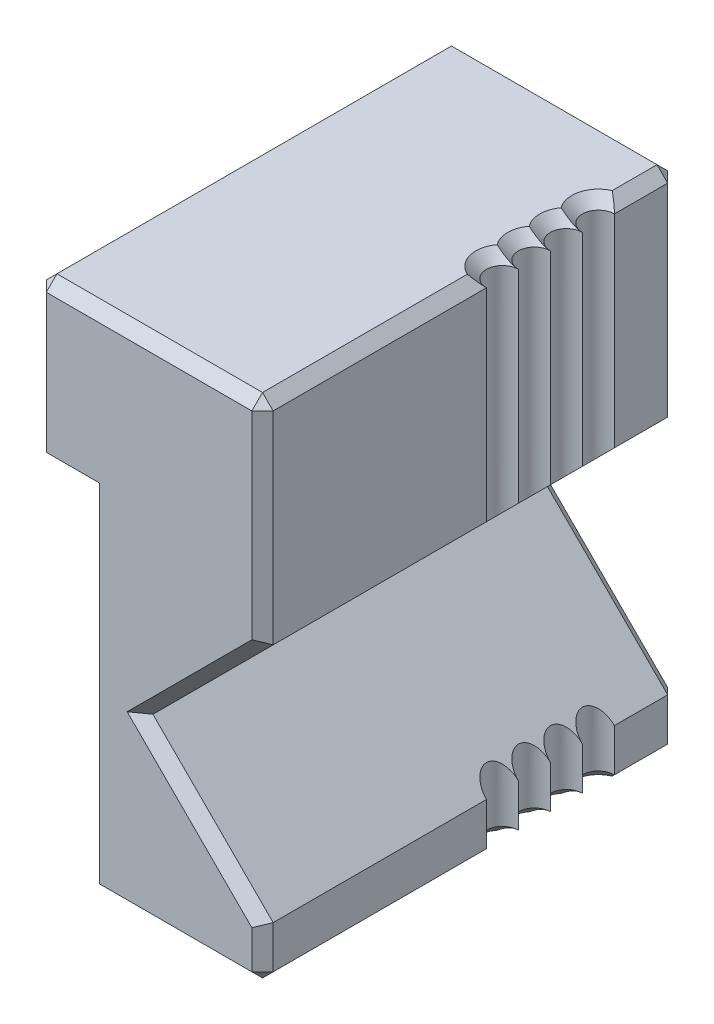
SolidWorks part; units mm, degrees
ref_plane "Front Plane" through (0, 0, 0) normal (0, 0, 1) x (1, 0, 0)
ref_plane "Top Plane" through (0, 0, 0) normal (0, 1, 0) x (1, 0, 0)
ref_plane "Right Plane" through (0, 0, 0) normal (1, 0, 0) x (0, 0, -1)
sketch "Sketch1" plane through (0, 0, 0) normal (0, 0, 1) x (1, 0, 0)
  line L0 (-11.2784, 0) -> (0, 11.2784)
  line L1 (0, 11.2784) -> (0, 31.2784)
  line L2 (0, 31.2784) -> (-21.2784, 31.2784)
  line L3 (-21.2784, 31.2784) -> (-21.2784, 16.2784)
  line L4 (-21.2784, 16.2784) -> (-16.2784, 16.2784)
  line L5 (-16.2784, 16.2784) -> (-16.2784, -16.2784)
  line L6 (-16.2784, -16.2784) -> (0, -16.2784)
  line L7 (0, -16.2784) -> (0, -11.2784)
  line L8 (0, -11.2784) -> (-11.2784, 0)
  circle A0 centre (0, 0) radius 7.975 construction
  dimension "D1" = 15.95
  dimension "D2" = 0
  dimension "D3" = 5
  dimension "D4" = 15
  dimension "D5" = 5
  dimension "D6" = 5
  dimension "D7" = 20
extrude "Boss-Extrude1" add sketch "Sketch1" along normal blind 39
sketch "Sketch2" plane through (0, 31.2784, 0) normal (0, 1, 0) x (1, 0, 0)
  circle A0 centre (0, -7.5) radius 1.5
  dimension "D1" = 3
  dimension "D2" = 6
extrude "Cut-Extrude1" cut sketch "Sketch2" against normal through all
pattern_linear "LPattern2" count 10 spacing 3 along (0, 0, 1) skipping (4, 0), (5, 0), (6, 0), (7, 0), (8, 0), (9, 0) of "Cut-Extrude1"
chamfer "Chamfer2" distance 1 angle 45 33 edges at (-1.5, 31.2784, 16.5) (-1.5, 31.2784, 13.5) (-1.5, 31.2784, 10.5) (-1.5, 31.2784, 7.5) (0, 31.2784, 3) (-1.5, -16.2784, 16.5) (-1.5, -16.2784, 13.5) (-1.5, -16.2784, 10.5) (-1.5, -16.2784, 7.5) (0, -16.2784, 3) (0, -13.7784, 39) (-8.1392, -16.2784, 39) (-18.7784, 16.2784, 39) (-5.6392, -5.6392, 39) (-5.6392, 5.6392, 39) (0, 21.2784, 39) (-10.6392, 31.2784, 39) (-5.6392, 5.6392, 0) (0, 21.2784, 0) (-10.6392, 31.2784, 0) (-21.2784, 31.2784, 19.5) (-21.2784, 23.7784, 39) (-21.2784, 16.2784, 19.5) (-21.2784, 23.7784, 0) (-18.7784, 16.2784, 0) (-5.6392, -5.6392, 0) (0, -13.7784, 0) (-8.1392, -16.2784, 0) (-16.2784, 0, 39) (-16.2784, -16.2784, 19.5) (-16.2784, 0, 0) (0, 31.2784, 28.5) (0, -16.2784, 28.5)
equation "\"Drill Bit OD\"=3"
equation "\"Shaft OD\"= 15.95"
equation "\"Number of Holes\"= 5"
equation "\"Face Gap\"= 0"
equation "\"D1@Sketch1\"=\"Shaft OD\""
equation "\"D2@Sketch1\"=\"Face Gap\" / 2"
equation "\"D1@Boss-Extrude1\"=(\"Number of Holes\" + 1.5) * \"Drill Bit OD\" * 2"
equation "\"D1@Sketch2\"=\"Drill Bit OD\""
equation "\"D3@LPattern2\"=\"Drill Bit OD\""
equation "\"D1@LPattern2\"=\"Number of Holes\"*2"
equation "\"D2@Sketch2\"=\"Drill Bit OD\"*2"
